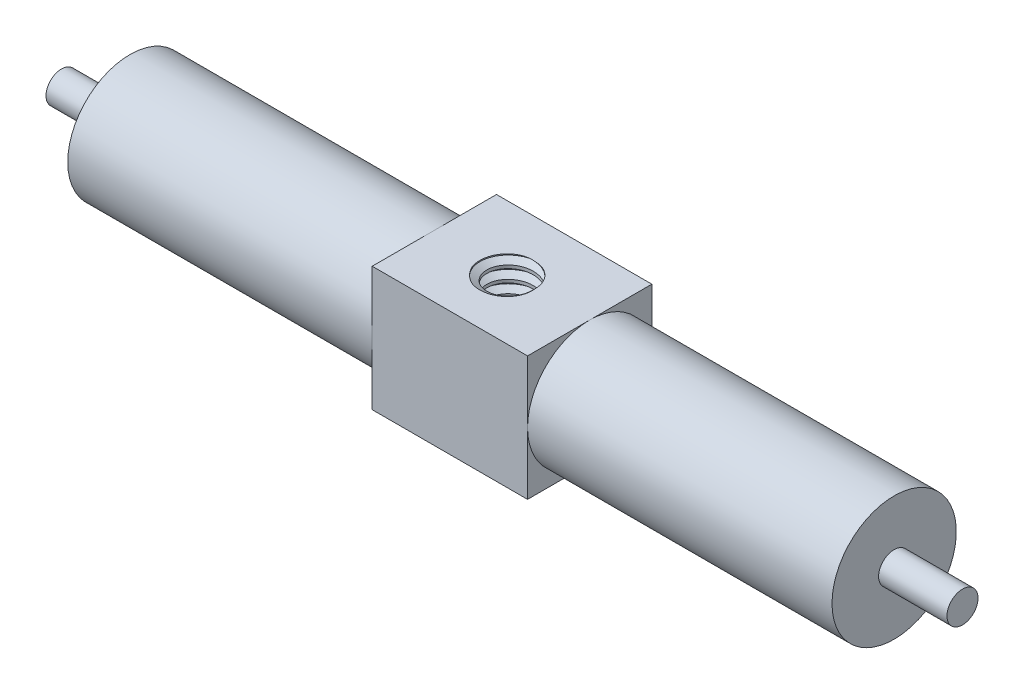
SolidWorks part; units mm, degrees
ref_plane "Front Plane" through (0, 0, 0) normal (0, 0, 1) x (1, 0, 0)
ref_plane "Top Plane" through (0, 0, 0) normal (0, 1, 0) x (1, 0, 0)
ref_plane "Right Plane" through (0, 0, 0) normal (1, 0, 0) x (0, 0, -1)
sketch "Sketch1" plane through (0, 0, 0) normal (0, 0, 1) x (1, 0, 0)
  line L0 (-145, 0) -> (145, 0) construction
  line L1 (-145, 0) -> (-145, 5)
  line L2 (-145, 5) -> (-123, 5)
  line L3 (-123, 5) -> (-123, 20)
  line L4 (-123, 20) -> (123, 20)
  line L5 (123, 20) -> (123, 5)
  line L6 (123, 5) -> (145, 5)
  line L7 (145, 5) -> (145, 0)
  line L8 (-145, 0) -> (145, 0)
  dimension "D1" = 290
  dimension "D2" = 5
  dimension "D3" = 20
  dimension "D4" = 22
  dimension "D5" = 22
  dimension "D6" = 145
  dimension "D7" = 145
revolve "Revolve1" add sketch "Sketch1" angle 360 about L0
sketch "Sketch2" plane through (0, 0, 0) normal (0, 1, 0) x (1, 0, 0)
  line L0 (-123, -20) -> (123, -20) construction
  line L1 (-25, 20) -> (25, 20)
  line L2 (-25, 20) -> (-25, -20)
  line L3 (-25, -20) -> (25, -20)
  line L4 (25, 20) -> (25, -20)
  line L5 (-25, 20) -> (25, -20) construction
  line L6 (-25, -20) -> (25, 20) construction
  line L8 (-123, 20) -> (-123, -20) construction
  line L9 (123, -20) -> (123, 20) construction
  point P0 (0, 0)
  dimension "D1" = 50
  dimension "D2" = 40
  dimension "D3" = 98
  dimension "D4" = 98
extrude "Boss-Extrude1" add sketch "Sketch2" along normal mid plane 40
sketch "Sketch3" plane through (0, 20, 0) normal (0, 1, 0) x (1, 0, 0)
  circle A0 centre (0, 0) radius 7.5
  dimension "D1" = 15
extrude "Cut-Extrude1" cut sketch "Sketch3" against normal through all
thread "Thread1" pitch 4 method cut profile "Thread Profile1" start angle 0, offset 0, length 40, pitch 4, diameter 15
ref_plane "Plane1" through (7.5, -20, 0) normal (0, 0, 1) x (1, 0, 0)
sketch "Thread Profile1" plane through (7.5, -20, 0) normal (0, 0, 1) x (1, 0, 0)
  line L0 (0, 0) -> (0, 4) construction
  line L1 (0, 0) -> (2.1651, 1.25)
  line L2 (2.1651, 1.25) -> (2.1651, 1.75)
  line L3 (2.1651, 1.75) -> (0, 3)
  line L4 (2.1651, 1.5) -> (0, 1.5) construction
  line L11 (0, 0) -> (0, 3)
  point P2 (0, 0)
  dimension "Pitch" = 4
  dimension "Profile_Angle" = 60
  dimension "Profile_Land" = 0.5
  dimension "Profile_Height" = 2.1651
